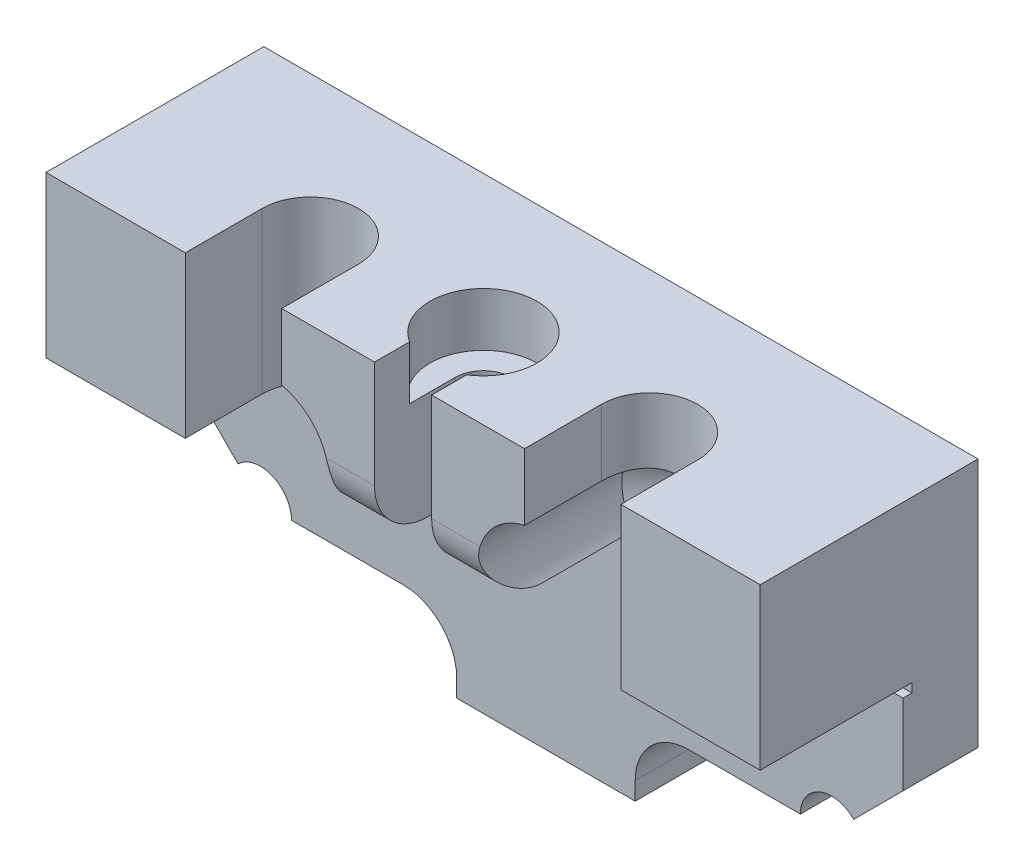
SolidWorks part; units mm, degrees
material "Custom Plastic"
ref_plane "Front Plane" through (0, 0, 0) normal (0, 0, 1) x (1, 0, 0)
ref_plane "Top Plane" through (0, 0, 0) normal (0, 1, 0) x (1, 0, 0)
ref_plane "Right Plane" through (0, 0, 0) normal (1, 0, 0) x (0, 0, -1)
sketch "Sketch1" plane through (0, 0, 0) normal (0, 0, 1) x (1, 0, 0)
  line L1 (-20, 0) -> (20, 0)
  line L2 (-20, 0) -> (-20, 22)
  line L3 (-20, 22) -> (20, 22)
  line L4 (20, 0) -> (20, 22)
  dimension "D2" = 40
  dimension "D3" = 22
extrude "Boss-Extrude1" add sketch "Sketch1" along normal blind 12.5
sketch "Sketch2" plane through (0, 0, 12.5) normal (0, 0, 1) x (1, 0, 0)
  line L0 (0, 14) -> (0, 15) construction
  line L2 (-7.5, 15) -> (7.5, 15) construction
  line L3 (20, 22) -> (-20, 22) construction
  line L4 (-7.5, 11) -> (-7.5, 19) construction
  line L5 (-9.15, 11) -> (-9.15, 19) construction
  line L6 (-5.85, 11) -> (-5.85, 19) construction
  line L7 (7.5, 11) -> (7.5, 19) construction
  line L8 (5.85, 11) -> (5.85, 19) construction
  line L9 (9.15, 11) -> (9.15, 19) construction
  line L10 (-16, 14) -> (16, 14) construction
  arc A0 (-9.15, 11) -> (-5.85, 11) centre (-7.5, 11) ccw construction
  arc A1 (-5.85, 19) -> (-9.15, 19) centre (-7.5, 19) ccw construction
  arc A2 (5.85, 11) -> (9.15, 11) centre (7.5, 11) ccw construction
  arc A3 (9.15, 19) -> (5.85, 19) centre (7.5, 19) ccw construction
  circle A4 centre (-16, 14) radius 1.7784 construction
  circle A5 centre (16, 14) radius 1.7784 construction
  circle A6 centre (-7.5, 15) radius 1.65
  circle A7 centre (7.5, 15) radius 1.65
  point P8 (-7.5, 15)
  point P15 (7.5, 15)
  dimension "D1" = 1.65
  dimension "D2" = 8
  dimension "D3" = 7
  dimension "D4" = 15
  dimension "D5" = 1
  dimension "D6" = 32
extrude "Cut-Extrude1" cut sketch "Sketch2" against normal through all
sketch "Sketch5" plane through (0, 22, 0) normal (0, 1, 0) x (1, 0, 0)
  line L0 (-12.2, -8.2) -> (-12.2, -12.5)
  line L1 (20, -12.5) -> (-20, -12.5) construction
  line L3 (-12.2, -12.5) -> (-6.8, -12.5)
  line L4 (-6.8, -12.5) -> (-6.8, -8.2)
  arc A0 (-6.8, -8.2) -> (-12.2, -8.2) centre (-9.5, -8.2) ccw
  dimension "D2" = 5.4
  dimension "D1" = 4.3
  dimension "D3" = 9.5
extrude "Cut-Extrude4" cut sketch "Sketch5" against normal through all
sketch "Sketch6" plane through (20, 0, 0) normal (1, 0, 0) x (0, 0, -1)
  line L0 (-12.5, 13) -> (-4.5, 13)
  line L1 (-12.5, 0) -> (-12.5, 22) construction
  line L3 (-4.5, 13) -> (-4.5, 0)
  line L4 (-12.5, 0) -> (0, 0) construction
  line L5 (-4.5, 0) -> (-12.5, 0)
  line L6 (-12.5, 0) -> (-12.5, 13)
  line L8 (-12.5, 22) -> (0, 22) construction
  line L9 (0, 0) -> (0, 22) construction
  dimension "D1" = 9
  dimension "D2" = 4.5
extrude "Cut-Extrude5" cut sketch "Sketch6" against normal through all
sketch "Sketch8" plane through (0, 22, 0) normal (0, 1, 0) x (1, 0, 0)
  line L0 (-1.6, -8) -> (-1.6, -12.5)
  line L2 (20, -12.5) -> (-6.8, -12.5) construction
  line L3 (-1.6, -12.5) -> (1.6, -12.5)
  line L4 (1.6, -12.5) -> (1.6, -8)
  arc A0 (1.6, -8.2) -> (-1.6, -8.2) centre (0, -8.2) ccw construction
  arc A1 (1.6, -8) -> (-1.6, -8) centre (0, -8) ccw
  point P7 (-9.5, -8.2)
  dimension "D1" = 1.6
  dimension "D2" = 0.2
extrude "Cut-Extrude7" cut sketch "Sketch8" against normal through all
sketch "Sketch9" plane through (0, 0, 12.5) normal (0, 0, 1) x (1, 0, 0)
  circle A0 centre (-7.5, 15) radius 3.35
  circle A1 centre (7.5, 15) radius 3.35
  dimension "D1" = 6.7
extrude "Cut-Extrude8" cut sketch "Sketch9" against normal up to surface (8 mm away) up to face at (0, 6.5, 4.5)
chamfer "Chamfer5" distance 1.8 angle 45 2 edges at (-7.5, 16.65, 4.5) (7.5, 16.65, 4.5)
chamfer "Chamfer6" [suppressed] distance 10 angle 45
sketch "Sketch11" plane through (0, 22, 0) normal (0, 1, 0) x (1, 0, 0)
  circle A0 centre (0, -8) radius 3
  arc A1 (1.6, -8) -> (-1.6, -8) centre (0, -8) ccw construction
  dimension "D1" = 6
extrude "Cut-Extrude9" cut sketch "Sketch11" against normal blind 3 contours A0
ref_plane "Plane1" through (0, 0, 0) normal (-1, 0, 0) x (0, 0, 1)
mirror "Mirror1" about plane through (0, 0, 0) normal (-1, 0, 0) of "Cut-Extrude4"
sketch "Sketch12" plane through (0, 0, 4.5) normal (0, 0, 1) x (1, 0, 0)
  line L0 (-16, 4) -> (16, 4) construction
  line L1 (0, 6.875) -> (0, -6.875) construction
  line L2 (-20, 13) -> (-12.2, 13) construction
  line L3 (17.2374, 5.2374) -> (20, 8)
  line L4 (20, 0) -> (20, 13) construction
  line L5 (20, 8) -> (20, 0)
  line L6 (20, 0) -> (5, 0)
  line L7 (-20, 0) -> (-20, 8)
  line L8 (-20, 0) -> (-20, 13) construction
  line L9 (-20, 8) -> (-17.2374, 5.2374)
  line L10 (-14.25, 4) -> (-5, 4)
  line L11 (5, 4) -> (14.25, 4)
  line L12 (-5, 0) -> (5, 0) construction
  line L13 (-5, 0) -> (-5, 4)
  line L14 (-5, 0) -> (-20, 0)
  line L15 (5, 0) -> (5, 4)
  arc A0 (-14.25, 4) -> (-17.2374, 5.2374) centre (-16, 4) ccw
  arc A1 (17.2374, 5.2374) -> (14.25, 4) centre (16, 4) ccw
  point P4 (0, 4)
  dimension "D2" = 3.5
  dimension "D1" = 32
  dimension "D3" = 9
  dimension "D4" = 10
extrude "Cut-Extrude10" cut sketch "Sketch12" against normal through all
sketch "Sketch13" plane through (20, 0, 0) normal (1, 0, 0) x (0, 0, -1)
  line L1 (-4.5, 13) -> (-4, 13)
  line L2 (-4.5, 13) -> (-4.5, 12.5)
  line L3 (-4.5, 12.5) -> (-4, 12.5)
  line L4 (-4, 13) -> (-4, 12.5)
  dimension "D1" = 0.5
extrude "Cut-Extrude11" cut sketch "Sketch13" against normal through all
fillet "Fillet1" radius 3 2 edges at (-5, 4, 2.25) (5, 4, 2.25)
chamfer "Chamfer7" distance 0.3 angle 45 16 edges at (0, 22, 0) (-20, 15, 0) (0, 0, 0) (20, 15, 0) (-5.85, 15, 0) (9.15, 15, 0) (-18.6187, 6.6187, 0) (-15.3303, 5.6168, 0) (-11.125, 4, 0) (15.3303, 5.6168, 0) (18.6187, 6.6187, 0) (-5.8787, 3.1213, 0) (-5, 0.5, 0) (5, 0.5, 0) (5.8787, 3.1213, 0) (11.125, 4, 0)
fillet "Fillet2" radius 3 2 edges at (-3.2063, 13, 12.5) (3.2063, 13, 12.5)
equation "\"y-cross-rib-thickness\"=6"
equation "\"y-rib-thickness\"=6"
equation "\"bed-plate-thickness\"=6"
equation "\"x-plate-thickness\"=5"
equation "\"rod-diameter\"=12"
equation "\"t-nut-hole-diameter\"=3"
equation "\"y-plate-thickness\"=5"
equation "\"enclosure-thickness\"=0.6"
equation "\"M3-Clearance\"=3.3"
equation "\"M4-Clearance\"=4.3"
equation "\"M5-Clearance\"=5.3"
equation "\"M6-Clearance\"=6.3"
equation "\"M8-Clearance\"=8.3"
equation "\"623-Bearing-Dia\"=11.2"
